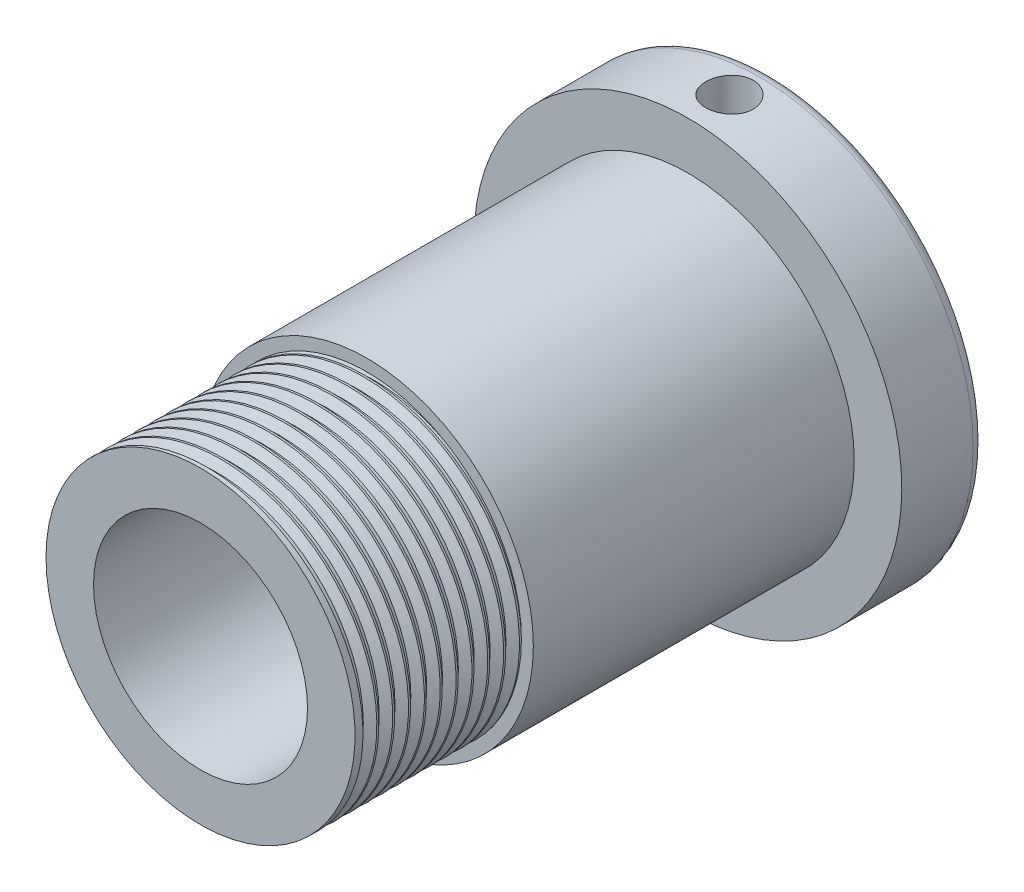
SolidWorks part; units mm, degrees
material "No.1 CI"
ref_plane "Front Plane" through (0, 0, 0) normal (0, 0, 1) x (1, 0, 0)
ref_plane "Top Plane" through (0, 0, 0) normal (0, 1, 0) x (1, 0, 0)
ref_plane "Right Plane" through (0, 0, 0) normal (1, 0, 0) x (0, 0, -1)
sketch "Sketch1" plane through (0, 0, 0) normal (1, 0, 0) x (0, 0, -1)
  line L0 (-27.6881, 0) -> (32693.9674, 0) construction
  line L1 (38.9514, 28.575) -> (38.9514, 0)
  line L2 (-37.2486, 0) -> (-37.2486, 20.6375)
  line L3 (-37.2486, 20.6375) -> (-15.0236, 20.6375)
  line L4 (-15.0236, 20.6375) -> (-15.0236, 22.225)
  line L5 (-15.0236, 22.225) -> (27.8389, 22.225)
  line L6 (27.8389, 22.225) -> (27.8389, 28.575)
  line L7 (27.8389, 28.575) -> (38.9514, 28.575)
  line L8 (38.9514, 0) -> (-37.2486, 0)
  dimension "D1" = 22.225
  dimension "D2" = 76.2
  dimension "D3" = 42.8625
  dimension "D4" = 41.275
  dimension "D5" = 44.45
  dimension "D6" = 57.15
revolve "Revolve1" add sketch "Sketch1" angle 360 about L0
sketch "Sketch5" plane through (0, 0, 37.2486) normal (0, 0, 1) x (1, 0, 0)
  circle A0 centre (0, 0) radius 14.2875
  dimension "D1" = 28.575
extrude "Cut-Extrude1" cut sketch "Sketch5" against normal through all
ref_plane "Plane1" through (0, 28.575, 0) normal (0, 1, 0) x (1, 0, 0)
sketch "Sketch6" plane through (0, 28.575, 0) normal (0, 1, 0) x (1, 0, 0)
  line L0 (28.575, 38.9514) -> (-28.575, 38.9514) construction
  line L1 (28.575, 38.9514) -> (-28.575, 38.9514) construction
  line L2 (0, 38.9514) -> (0, -49961.0486) construction
  circle A0 centre (0, 33.3951) radius 3.175
  point P4 (0, 38.9514)
  dimension "D1" = 6.35
  dimension "D2" = 5.5562
extrude "Cut-Extrude2" cut sketch "Sketch6" against normal blind 9.525 contours A0
fillet "Fillet1" radius 1.5875 1 edges at (28.575, 0, -38.9514)
ref_plane "Plane2" through (0, 0, 14.986) normal (0, 0, 1) x (1, 0, 0)
thread "Thread1" pitch 2.1167 method cut profile "Thread Profile1" start angle 0, offset 0, length 0, pitch 2.1167, diameter 41.275
ref_plane "Plane3" through (-20.6375, 0, 37.2486) normal (0, -1, 0) x (-1, 0, 0)
sketch "Thread Profile1" plane through (-20.6375, 0, 37.2486) normal (0, -1, 0) x (-1, 0, 0)
  line L0 (0, 0) -> (0, 2.1167) construction
  line L11 (0, 0) -> (0, 1.8521)
  line L12 (0, 1.8521) -> (-1.1457, 1.1906)
  line L13 (-1.1457, 1.1906) -> (-1.1457, 0.6615)
  line L15 (-1.1457, 0.6615) -> (0, 0)
  line L17 (-1.1457, 0.926) -> (0, 0.926) construction
  point P2 (0, 0)
  dimension "Pitch" = 2.1167
  dimension "Profile_Angle" = 60
  dimension "Profile_Land" = 0.5292
  dimension "Profile_Height" = 1.1457
